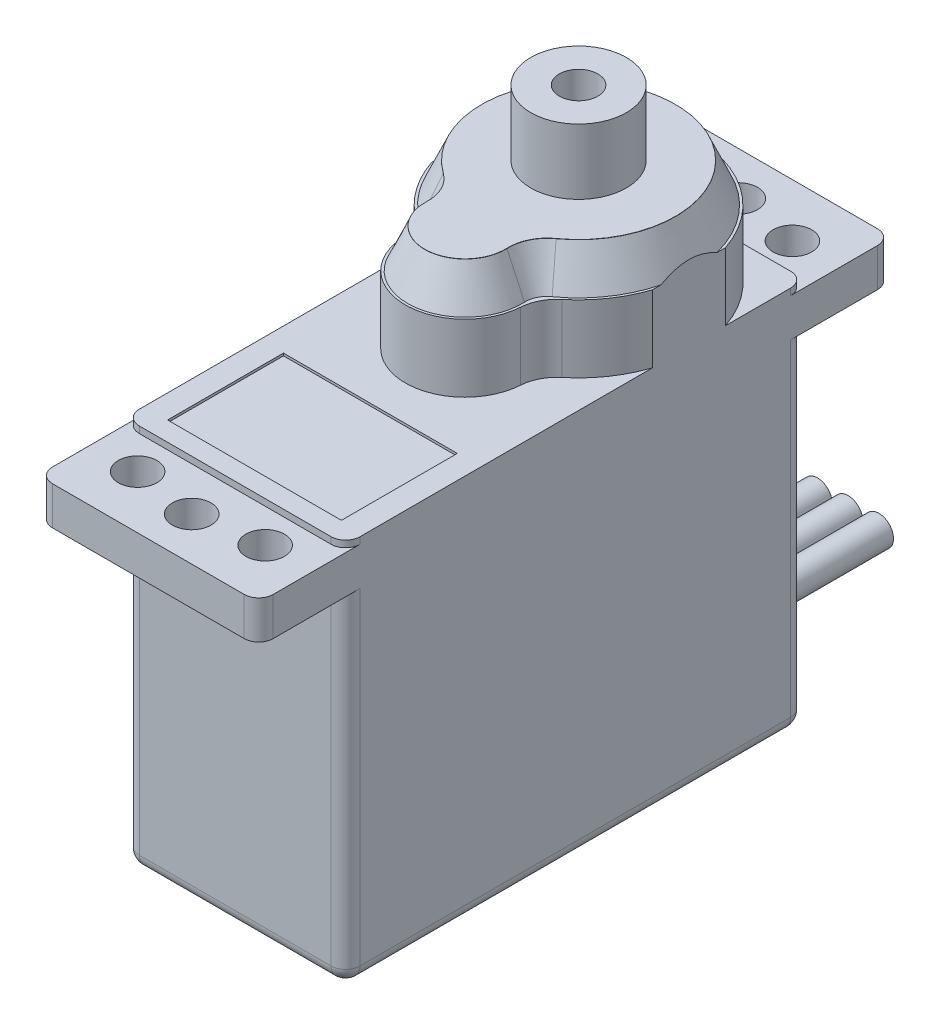
SolidWorks part; units mm, degrees
material "Mini Servo"
ref_plane "Front Plane" through (0, 0, 0) normal (0, 0, 1) x (1, 0, 0)
ref_plane "Top Plane" through (0, 0, 0) normal (0, 1, 0) x (1, 0, 0)
ref_plane "Right Plane" through (0, 0, 0) normal (1, 0, 0) x (0, 0, -1)
sketch "Sketch1" plane through (0, 0, 0) normal (1, 0, 0) x (0, 0, -1)
  line L0 (0, 10) -> (0, -10) construction
  line L1 (-11.8999, 10) -> (11.8999, 10)
  line L2 (-11.8999, 10) -> (-11.8999, -10)
  line L3 (-11.8999, -10) -> (11.8999, -10)
  line L4 (11.8999, 10) -> (11.8999, -10)
  dimension "D1" = 23.7998
  dimension "D2" = 20
extrude "Extrude1" add sketch "Sketch1" along normal blind 5.715 and the other way blind 5.715
sketch "Sketch2" plane through (0, 10, 0) normal (0, 1, 0) x (-1, 0, 0)
  line L3 (0, 0) -> (0, -5.8801) construction
  line L4 (0, 3.0861) -> (5.715, 3.0861) construction
  line L5 (-5.715, -11.8999) -> (5.715, -11.8999) construction
  line L6 (5.715, -11.8999) -> (5.715, 11.8999) construction
  line L7 (5.715, -7.7713) -> (5.715, -3.9889)
  line L8 (-5.715, -11.8999) -> (-5.715, 11.8999) construction
  line L9 (-5.715, -7.7713) -> (-5.715, -3.9889)
  arc A0 (-3.0128, -0.6685) -> (-5.715, -3.9889) centre (0, -5.8801) ccw
  arc A1 (3.0128, -0.6685) -> (-3.0128, -0.6685) centre (0, 0) ccw
  arc A2 (5.715, -3.9889) -> (3.0128, -0.6685) centre (0, -5.8801) ccw
  arc A3 (-5.715, -7.7713) -> (5.715, -7.7713) centre (0, -5.8801) ccw
  dimension "D2" = 6.1722
  dimension "D1" = 6.0198
extrude "Boss-Extrude7" add sketch "Sketch2" along normal blind 3.5
sketch "Sketch10" plane through (0, 13.5, 0) normal (0, 1, 0) x (1, 0, 0)
  line L4 (4.715, 4.1576) -> (4.715, 7.6026)
  line L5 (-4.715, 7.6026) -> (-4.715, 4.1576)
  arc A8 (-1.7289, 1.1674) -> (1.7289, 1.1674) centre (0, 0) ccw
  arc A9 (1.7289, 1.1674) -> (4.715, 4.1576) centre (0, 5.8801) ccw
  arc A10 (4.715, 7.6026) -> (-4.715, 7.6026) centre (0, 5.8801) ccw
  arc A11 (-4.715, 4.1576) -> (-1.7289, 1.1674) centre (0, 5.8801) ccw
  arc A12 (-1.7289, 1.1674) -> (1.7289, 1.1674) centre (0, 0) ccw
  arc A13 (1.7289, 1.1674) -> (-1.7289, 1.1674) centre (0, 5.8801) ccw
  dimension "D1" = 1
extrude "Boss-Extrude8" add sketch "Sketch10" along normal blind 2
sketch "Sketch3" plane through (5.715, 0, 0) normal (1, 0, 0) x (0, 0, -1)
  line L1 (-11.8999, 9.658) -> (-16.3957, 9.658)
  line L2 (-11.8999, 9.658) -> (-11.8999, 7.6768)
  line L3 (-11.8999, 7.6768) -> (-16.3957, 7.6768)
  line L4 (-16.3957, 9.658) -> (-16.3957, 7.6768)
  line L5 (-11.8999, 10) -> (-11.8999, -10) construction
  line L6 (0, 8.509) -> (0, -10) construction
  line L7 (11.8999, 9.658) -> (16.3957, 9.658)
  line L8 (11.8999, 9.658) -> (11.8999, 7.6768)
  line L9 (11.8999, 7.6768) -> (16.3957, 7.6768)
  line L10 (16.3957, 9.658) -> (16.3957, 7.6768)
  line L11 (-11.8999, -10) -> (11.8999, -10) construction
  line L12 (10.8999, 15.5) -> (1.1674, 15.5) construction
  dimension "D1" = 4.4958
  dimension "D2" = 1.9812
  dimension "D3" = 5.842
extrude "Extrude2" add sketch "Sketch3" against normal up to surface (11.43 mm away) up to face at (-5.715, 6.3125, -4.1911)
sketch "Sketch4" plane through (0, 9.658, 0) normal (0, 1, 0) x (1, 0, 0)
  line L0 (0, 16.3957) -> (0, -16.3957) construction
  line L1 (-5.715, 16.3957) -> (5.715, 16.3957) construction
  line L2 (-5.715, -16.3957) -> (5.715, -16.3957) construction
  line L3 (-5.715, 0) -> (5.715, 0) construction
  line L4 (-5.715, -11.8999) -> (-5.715, -16.3957) construction
  line L5 (5.715, -11.8999) -> (5.715, -16.3957) construction
  line L7 (-3.302, -13.65) -> (3.302, -13.65) construction
  line L8 (-3.302, -13.65) -> (-3.302, 13.65) construction
  line L9 (-3.302, 13.65) -> (3.302, 13.65) construction
  line L10 (3.302, -13.65) -> (3.302, 13.65) construction
  line L11 (-3.302, -13.65) -> (3.302, 13.65) construction
  line L12 (-3.302, 13.65) -> (3.302, -13.65) construction
  circle A0 centre (0, 14.15) radius 1
  circle A1 centre (0, -14.15) radius 1
  circle A2 centre (-3.302, 13.65) radius 1
  circle A3 centre (3.302, 13.65) radius 1
  circle A4 centre (3.302, -13.65) radius 1
  circle A5 centre (-3.302, -13.65) radius 1
  point P17 (0, 0)
  dimension "D2" = 2
  dimension "D1" = 28.3
  dimension "D3" = 6.604
  dimension "D4" = 27.3
extrude "Extrude3" cut sketch "Sketch4" against normal through all
sketch "Sketch5" plane through (0, 0, -11.8999) normal (0, 0, -1) x (-1, 0, 0)
  line L0 (0, 0) -> (0, -9.492) construction
  line L1 (-3.175, -9.492) -> (3.175, -9.492)
  line L2 (-3.175, -9.492) -> (-3.175, -5.047)
  line L3 (-3.175, -5.047) -> (3.175, -5.047)
  line L4 (3.175, -9.492) -> (3.175, -5.047)
  line L5 (-5.715, -10) -> (5.715, -10) construction
  dimension "D1" = 0.508
  dimension "D2" = 6.35
  dimension "D3" = 4.445
extrude "Boss-Extrude1" add sketch "Sketch5" along normal blind 1.5875
sketch "Sketch6" plane through (0, 0, -13.4874) normal (0, 0, -1) x (-1, 0, 0)
  line L0 (-3.175, -7.2695) -> (0, -7.2695) construction
  line L1 (-3.175, -5.047) -> (-3.175, -9.492) construction
  line L2 (0, -7.2695) -> (3.175, -7.2695) construction
  line L3 (3.175, -9.492) -> (3.175, -5.047) construction
  circle A0 centre (0, -7.2695) radius 0.762
  circle A1 centre (-1.5875, -7.2695) radius 0.762
  circle A2 centre (1.5875, -7.2695) radius 0.762
  dimension "D1" = 1.524
extrude "Boss-Extrude4" add sketch "Sketch6" along normal blind 6.35
sketch "Sketch8" plane through (0, 15.5, 0) normal (0, 1, 0) x (1, 0, 0)
  circle A0 centre (0, 5.8801) radius 2.4765
  arc A1 (1.7289, 1.1674) -> (-1.7289, 1.1674) centre (0, 5.8801) ccw construction
  dimension "D1" = 4.953
extrude "Boss-Extrude6" add sketch "Sketch8" along normal blind 3.3782
sketch "Sketch9" plane through (0, 10, 0) normal (0, 1, 0) x (1, 0, 0)
  line L0 (0, 0) -> (0, -11.8999) construction
  line L2 (-5.715, -11.8999) -> (5.715, -11.8999) construction
  line L3 (-4.5, -10.8999) -> (4.5, -10.8999)
  line L4 (-4.5, -10.8999) -> (-4.5, -4.8999)
  line L5 (-4.5, -4.8999) -> (4.5, -4.8999)
  line L6 (4.5, -10.8999) -> (4.5, -4.8999)
  line L7 (-4.5, -10.8999) -> (4.5, -4.8999) construction
  line L8 (-4.5, -4.8999) -> (4.5, -10.8999) construction
  line L9 (5.715, -11.8999) -> (-5.715, -11.8999) construction
  point P5 (0, -7.8999)
  dimension "D1" = 6
  dimension "D2" = 9
  dimension "D3" = 1
extrude "Cut-Extrude2" cut sketch "Sketch9" against normal blind 0.125
sketch "Sketch11" plane through (0, 18.8782, 0) normal (0, 1, 0) x (1, 0, 0)
  circle A0 centre (0, 5.8801) radius 1
  dimension "D1" = 2
extrude "Cut-Extrude3" cut sketch "Sketch11" against normal blind 2
fillet "Fillet1" radius 0.75 16 edges at (-5.715, 8.6674, -16.3957) (-5.715, -1.1616, -11.8999) (-5.715, 9.829, -11.8999) (5.715, 8.6674, -16.3957) (5.715, 9.829, -11.8999) (5.715, 8.6674, 16.3957) (-5.715, 8.6674, 16.3957) (0, -10, 11.8999) (0, -10, -11.8999) (-5.715, -10, 0) (5.715, -10, 0) (5.715, -1.1616, -11.8999)
fillet "Fillet2" radius 2 4 edges at (3.0128, 11.75, -0.6685) (-3.0128, 11.75, -0.6685) (1.7289, 14.5, -1.1674) (-1.7289, 14.5, -1.1674)
chamfer "Chamfer1" distance 0.875 angle 66.25 4 edges at (-2.2854, 13.5, -1.0473) (0, 13.5, 2.0861) (2.2854, 13.5, -1.0473) (0, 13.5, -10.8999) first distance on face at (0, 13.5, -3.3352)
